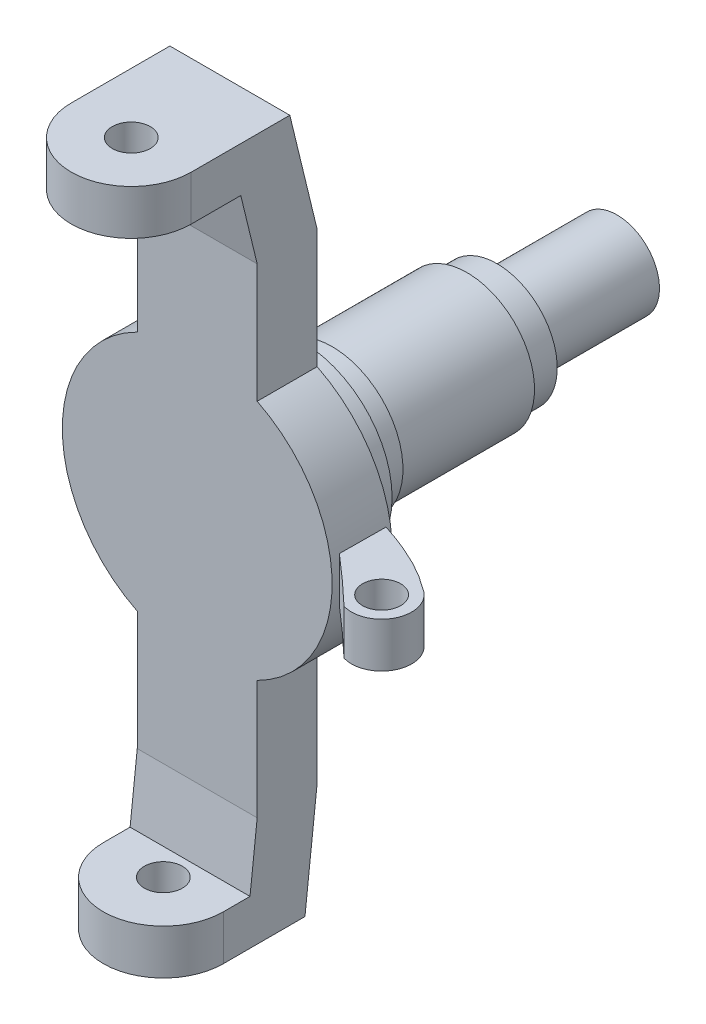
SolidWorks part; units mm, degrees
ref_plane "Front Plane" through (0, 0, 0) normal (0, 0, 1) x (1, 0, 0)
ref_plane "Top Plane" through (0, 0, 0) normal (0, 1, 0) x (1, 0, 0)
ref_plane "Right Plane" through (0, 0, 0) normal (1, 0, 0) x (0, 0, -1)
sketch "Sketch1" plane through (0, 0, 0) normal (0, 0, 1) x (1, 0, 0)
  line L0 (-1000, 0) -> (49000, 0) construction
  line L1 (0, -1000) -> (0, 49000) construction
  line L3 (-20, 80) -> (20, 80)
  line L4 (-20, 80) -> (-20, -80)
  line L5 (-20, -80) -> (20, -80)
  line L6 (20, 80) -> (20, -80)
  line L7 (-20, 80) -> (20, -80) construction
  line L8 (-20, -80) -> (20, 80) construction
  circle A0 centre (0, 0) radius 45
  point P4 (0, 0)
extrude "Boss-Extrude1" add sketch "Sketch1" along normal blind 20 contours A0 L6 L3 L4 | L6 A0 L4 | L6 A0 | A0 L4 L5 L6 | L4 A0 region at (0, 61.7093, 0) region at (0, 0, 0) region at (-30.2844, 0, 0) region at (30.2844, 0, 0) region at (0, -61.7093, 0)
sketch "Sketch2" plane through (0, 0, 0) normal (1, 0, 0) x (0, 0, -1)
  line L0 (-20, 80) -> (0, 80)
  line L1 (0, 80) -> (-9.1169, 117.5)
  line L5 (-9.1169, 117.5) -> (-63.9165, 117.5)
  line L7 (-63.9165, 117.5) -> (-63.9165, 102.5)
  line L9 (-25.4702, 102.5) -> (-20, 80)
  line L10 (-63.9165, 102.5) -> (-25.4702, 102.5)
  dimension "D1" = 117.5
extrude "Boss-Extrude2" add sketch "Sketch2" along normal mid plane 40
sketch "Sketch3" plane through (0, 117.5, 0) normal (0, 1, 0) x (1, 0, 0)
  line L0 (-20, -9.1169) -> (-20, -63.9165) construction
  line L1 (20, -9.1169) -> (20, -63.9165) construction
  circle A0 centre (0, -42) radius 6.35
  arc A1 (-20, -42) -> (20, -42) centre (0, -42) ccw
sketch "Sketch4" plane through (0, 117.5, 0) normal (0, 1, 0) x (1, 0, 0)
  line L0 (-20, -42) -> (-20, -63.9165)
  line L1 (-20, -63.9165) -> (20, -63.9165)
  line L2 (20, -63.9165) -> (20, -42)
  arc A0 (-20, -42) -> (20, -42) centre (0, -42) ccw
  arc A1 (-20, -42) -> (20, -42) centre (0, -42) ccw construction
extrude "Cut-Extrude1" cut sketch "Sketch4" against normal blind 40
extrude "Cut-Extrude2" cut sketch "Sketch3" against normal blind 40 contours A0 region at (0, 117.5, 42)
sketch "Sketch5" plane through (0, 0, 0) normal (1, 0, 0) x (0, 0, -1)
  line L0 (-20, -80) -> (0, -80)
  line L1 (0, -80) -> (-4.0658, -116.5)
  line L2 (-4.0658, -116.5) -> (-57.1462, -116.5)
  line L3 (-57.1462, -116.5) -> (-57.1462, -101.5)
  line L4 (-57.1462, -101.5) -> (-22.3949, -101.5)
  line L5 (-22.3949, -101.5) -> (-20, -80)
  dimension "D1" = 36.5
extrude "Boss-Extrude3" add sketch "Sketch5" along normal mid plane 40
sketch "Sketch6" plane through (0, -116.5, 0) normal (0, -1, 0) x (1, 0, 0)
  line L0 (20, 57.1462) -> (20, 4.0658) construction
  circle A0 centre (0, 31.3) radius 6.35
  arc A1 (-20, 22.3949) -> (20, 40.2051) centre (0, 31.3) cw
  dimension "D1" = 31.3
extrude "Cut-Extrude4" cut sketch "Sketch6" against normal blind 40 contours A0
sketch "Sketch9" plane through (0, 0, 0) normal (0, 0, -1) x (-1, 0, 0)
  circle A0 centre (0, 0) radius 30
  circle A1 centre (0, 0) radius 23.625
  circle A2 centre (0, 0) radius 22.5
  circle A3 centre (0, 0) radius 20.075
  circle A4 centre (0, 0) radius 14.175
extrude "Boss-Extrude4" add sketch "Sketch9" along normal blind 15 contours A0 A1 region at (29.1515, 0, 0)
extrude "Boss-Extrude5" add sketch "Sketch9<3>" along normal blind 25 contours A1 A2 region at (22.9568, 0, 0)
sketch "Sketch9<3>" plane through (0, 0, 0) normal (0, 0, -1) x (-1, 0, 0) same geometry as "Sketch9"
extrude "Boss-Extrude6" add sketch "Sketch9<4>" along normal blind 70 contours A2 A3 region at (21.8636, 0, 0)
sketch "Sketch9<4>" plane through (0, 0, 0) normal (0, 0, -1) x (-1, 0, 0) same geometry as "Sketch9"
extrude "Boss-Extrude7" add sketch "Sketch9<5>" along normal blind 80 contours A3 A4 region at (19.5072, 0, 0)
sketch "Sketch9<5>" plane through (0, 0, 0) normal (0, 0, -1) x (-1, 0, 0) same geometry as "Sketch9"
extrude "Boss-Extrude8" add sketch "Sketch9<6>" along normal blind 120 contours A4 region at (0, 0, 0)
sketch "Sketch9<6>" plane through (0, 0, 0) normal (0, 0, -1) x (-1, 0, 0) same geometry as "Sketch9"
sketch "Sketch10" plane through (0, -101.5, 0) normal (0, 1, 0) x (1, 0, 0)
  line L0 (-20, -9.1169) -> (-20, -42) construction
  line L1 (20, -9.1169) -> (20, -42) construction
  line L2 (-20, -31.3) -> (-20, -57.1462)
  line L3 (-20, -57.1462) -> (20, -57.1462)
  line L4 (20, -57.1462) -> (20, -31.3)
  arc A0 (-20, -31.3) -> (20, -31.3) centre (0, -31.3) ccw
extrude "Cut-Extrude5" cut sketch "Sketch10" against normal blind 120
sketch "Sketch12" plane through (0, 0, 0) normal (0, 1, 0) x (1, 0, 0)
  line L0 (45, -20) -> (45, 0) construction
  line L1 (45, -2.0187) -> (44.8761, -17.4637)
  circle A0 centre (63.8, -22.3) radius 6.35
  arc A1 (60.836, -31.879) -> (68.7993, -13.608) centre (63.8, -22.3) ccw
  spline S0 degree 2 poles (44.8761, -17.4637) (53.4372, -24.802) (60.836, -31.879) knots 0 0 0 1 1 1
  spline S1 degree 2 poles (45, -2.0187) (59.8561, -6.7648) (68.7993, -13.608) knots 0 0 0 1 1 1
  point P0 (63.8, -22.3)
  dimension "D1" = 63.8
  dimension "D2" = 22.3
extrude "Boss-Extrude9" add sketch "Sketch12" along normal mid plane 15
